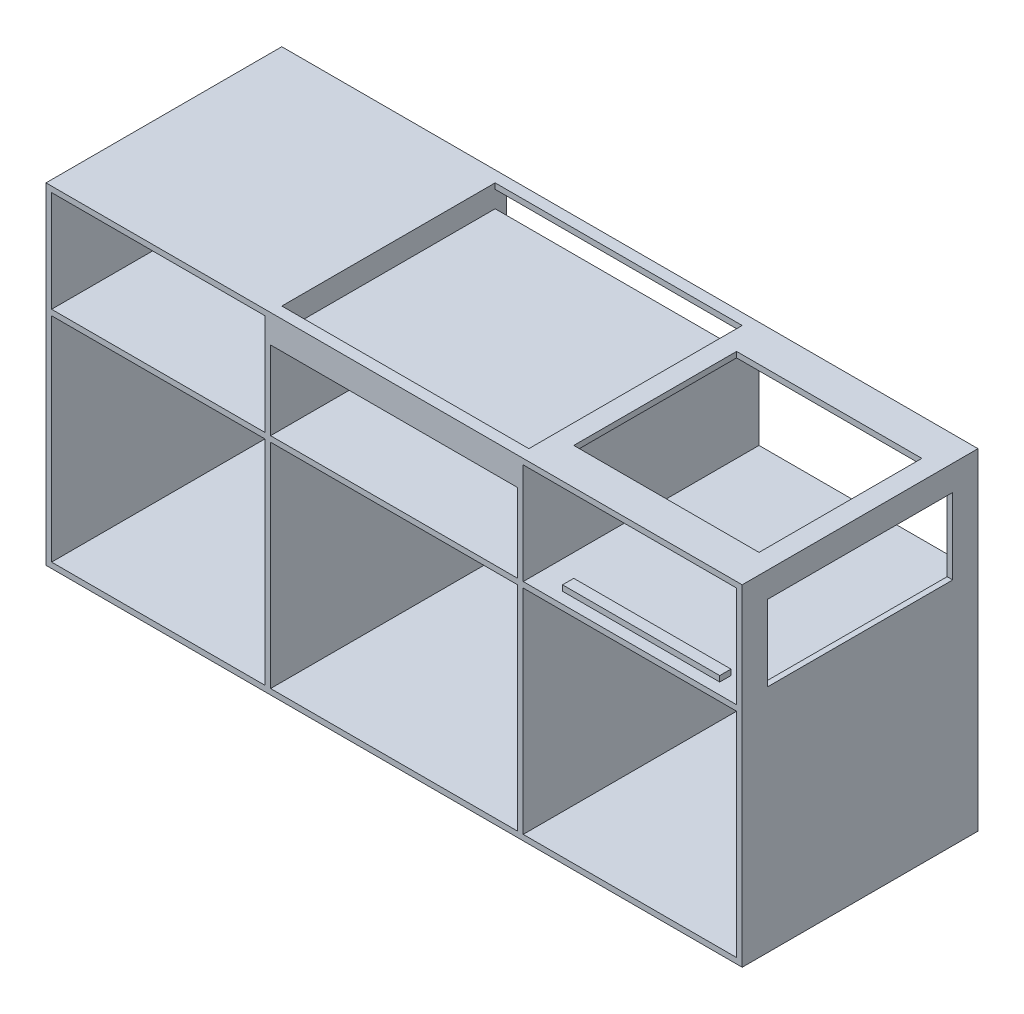
SolidWorks part; units mm, degrees
material "Erable"
ref_plane "Plan de face" through (0, 0, 0) normal (0, 0, 1) x (1, 0, 0)
ref_plane "Plan de dessus" through (0, 0, 0) normal (0, 1, 0) x (1, 0, 0)
ref_plane "Plan de droite" through (0, 0, 0) normal (1, 0, 0) x (0, 0, -1)
sketch "base" plane through (0, 0, 0) normal (0, 1, 0) x (1, 0, 0)
  line L0 (-3.1738, 188.5224) -> (-3.1738, -231.4776) construction
  line L1 (-613.1738, 188.5224) -> (606.8262, 188.5224)
  line L2 (-613.1738, 188.5224) -> (-613.1738, -231.4776)
  line L3 (-613.1738, -231.4776) -> (606.8262, -231.4776)
  line L4 (606.8262, 188.5224) -> (606.8262, -231.4776)
  line L5 (606.8262, -231.4776) -> (616.8262, -231.4776)
  line L6 (-613.1738, 188.5224) -> (-623.1738, 188.5224)
  line L7 (-613.1738, 188.5224) -> (-613.1738, -231.4776)
  line L8 (-613.1738, -231.4776) -> (-623.1738, -231.4776)
  line L9 (-623.1738, 188.5224) -> (-623.1738, -231.4776)
  line L10 (606.8262, 188.5224) -> (616.8262, 188.5224)
  line L11 (616.8262, 188.5224) -> (616.8262, -231.4776)
  line L13 (-233.1738, 188.5224) -> (-223.1738, 188.5224)
  line L14 (-233.1738, 188.5224) -> (-233.1738, -231.4776)
  line L15 (-233.1738, -231.4776) -> (-223.1738, -231.4776)
  line L16 (-223.1738, 188.5224) -> (-223.1738, -231.4776)
  line L17 (216.8262, 188.5224) -> (226.8262, 188.5224)
  line L18 (216.8262, 188.5224) -> (216.8262, -231.4776)
  line L19 (216.8262, -231.4776) -> (226.8262, -231.4776)
  line L20 (226.8262, 188.5224) -> (226.8262, -231.4776)
  dimension "D1" = 1220
  dimension "D2" = 420
  dimension "D3" = 10
  dimension "D4" = 10
  dimension "D5" = 380
  dimension "D6" = 10
  dimension "D7" = 380
extrude "planche_bas" add sketch "base" along normal blind 10 contours L1 L0 L3 L18 | L0 L1 L16 L3 | L1 L20 L3 L4 | L14 L1 L2 L3 region at (106.8262, 0, 21.4776) region at (-113.1738, 0, 21.4776) region at (-423.1738, 0, 21.4776) region at (416.8262, 0, 21.4776)
extrude "panneaux_lateraux" add sketch "base<6>" along normal blind 580 contours L11 L10 L4 L5 | L6 L9 L8 L2 region at (-618.1738, 0, 21.4776) region at (611.8262, 0, 21.4776)
sketch "base<6>" plane through (0, 0, 0) normal (0, 1, 0) x (1, 0, 0) same geometry as "base"
extrude "panneaux_bas_inter" add sketch "base<7>" along normal blind 390 contours L20 L1 L18 L3 | L16 L15 L14 L13 region at (221.8262, 0, 21.4776)
sketch "base<7>" plane through (0, 0, 0) normal (0, 1, 0) x (1, 0, 0) same geometry as "base"
ref_plane "Plan1" through (0, 390, 0) normal (0, 1, 0) x (1, 0, 0)
sketch "Esquisse2" plane through (0, 390, 0) normal (0, 1, 0) x (1, 0, 0)
  line L1 (-613.1738, 188.5224) -> (606.8262, 188.5224)
  line L2 (-613.1738, 188.5224) -> (-613.1738, -231.4776)
  line L3 (-613.1738, -231.4776) -> (606.8262, -231.4776)
  line L4 (606.8262, 188.5224) -> (606.8262, -231.4776)
  line L5 (-233.1738, 188.5224) -> (-223.1738, 188.5224)
  line L6 (-233.1738, 188.5224) -> (-233.1738, -231.4776)
  line L7 (-233.1738, -231.4776) -> (-223.1738, -231.4776)
  line L8 (-223.1738, 188.5224) -> (-223.1738, -231.4776)
  line L9 (216.8262, 188.5224) -> (226.8262, 188.5224)
  line L10 (216.8262, 188.5224) -> (216.8262, -231.4776)
  line L11 (216.8262, -231.4776) -> (226.8262, -231.4776)
  line L12 (226.8262, 188.5224) -> (226.8262, -231.4776)
  line L13 (276.8262, -191.4776) -> (556.8262, -191.4776)
  line L14 (276.8262, -191.4776) -> (276.8262, -211.4776)
  line L15 (276.8262, -211.4776) -> (556.8262, -211.4776)
  line L16 (556.8262, -191.4776) -> (556.8262, -211.4776)
  dimension "D1" = 50
  dimension "D2" = 50
  dimension "D3" = 20
  dimension "D4" = 20
extrude "Boss.-Extru.9" add sketch "Esquisse2" along normal blind 10 separate body contours L6 L1 L2 L3 | L10 L1 L8 L3 | L1 L12 L3 L4 region at (-423.1738, 390, 21.4776) region at (-3.1738, 390, 21.4776) region at (416.8262, 390, 14.9322)
extrude "Boss.-Extru.10" add sketch "Esquisse2<4>" along normal blind 190 contours L8 L7 L6 L5 | L10 L11 L12 L9
sketch "Esquisse2<4>" plane through (0, 390, 0) normal (0, 1, 0) x (1, 0, 0) same geometry as "Esquisse2"
ref_plane "Plan7" through (0, 580, 0) normal (0, 1, 0) x (1, 0, 0)
sketch "Esquisse5" plane through (0, 580, 0) normal (0, 1, 0) x (1, 0, 0)
  line L1 (-623.1738, 188.5224) -> (616.8262, 188.5224)
  line L2 (-623.1738, 188.5224) -> (-623.1738, -231.4776)
  line L3 (-623.1738, -231.4776) -> (616.8262, -231.4776)
  line L4 (616.8262, 188.5224) -> (616.8262, -231.4776)
  line L5 (251.8262, 123.5224) -> (581.8262, 123.5224)
  line L6 (251.8262, 123.5224) -> (251.8262, -166.4776)
  line L7 (251.8262, -166.4776) -> (581.8262, -166.4776)
  line L8 (581.8262, 123.5224) -> (581.8262, -166.4776)
  line L9 (-223.1738, 168.5224) -> (216.8262, 168.5224)
  line L10 (-223.1738, 168.5224) -> (-223.1738, -211.4776)
  line L11 (-223.1738, -211.4776) -> (216.8262, -211.4776)
  line L12 (216.8262, 168.5224) -> (216.8262, -211.4776)
  dimension "D1" = 35
  dimension "D2" = 65
  dimension "D3" = 65
  dimension "D4" = 330
  dimension "D5" = 20
  dimension "D6" = 20
  dimension "D7" = 35
  dimension "D8" = 440
extrude "Boss.-Extru.11" add sketch "Esquisse5" along normal blind 10
ref_plane "Plan8" through (0, 550, 0) normal (0, 1, 0) x (1, 0, 0)
sketch "Esquisse7" plane through (0, 550, 0) normal (0, 1, 0) x (1, 0, 0)
  line L1 (-223.1738, 168.5224) -> (216.8262, 168.5224)
  line L2 (-223.1738, 168.5224) -> (-223.1738, -211.4776)
  line L3 (-223.1738, -211.4776) -> (216.8262, -211.4776)
  line L4 (216.8262, 168.5224) -> (216.8262, -211.4776)
  line L5 (-223.1738, -211.4776) -> (216.8262, -211.4776)
  line L6 (-223.1738, -211.4776) -> (-223.1738, -231.4776)
  line L7 (-223.1738, -231.4776) -> (216.8262, -231.4776)
  line L8 (216.8262, -211.4776) -> (216.8262, -231.4776)
extrude "Boss.-Extru.12" add sketch "Esquisse7" against normal blind 10 contours L4 L1 L2 L3 region at (-3.1738, 550, 21.4776)
extrude "Boss.-Extru.13" add sketch "Esquisse7<3>" along normal blind 30 and the other way blind 10 contours L8 L3 L6 L7 region at (-3.1738, 550, 221.4776)
sketch "Esquisse7<3>" plane through (0, 550, 0) normal (0, 1, 0) x (1, 0, 0) same geometry as "Esquisse7"
sketch "Esquisse8" plane through (616.8262, 0, 0) normal (1, 0, 0) x (0, 0, -1)
  line L0 (-231.4776, 590) -> (188.5224, 590) construction
  line L1 (-186.4776, 545) -> (143.5224, 545)
  line L2 (-186.4776, 545) -> (-186.4776, 410)
  line L3 (-186.4776, 410) -> (143.5224, 410)
  line L4 (143.5224, 545) -> (143.5224, 410)
  line L5 (-231.4776, 590) -> (-231.4776, 0) construction
  line L6 (188.5224, 590) -> (188.5224, 0) construction
  dimension "D1" = 45
  dimension "D2" = 330
  dimension "D3" = 45
  dimension "D4" = 45
  dimension "D5" = 135
extrude "Enlèv. mat.-Extru.3" cut sketch "Esquisse8" against normal blind 10
extrude "Boss.-Extru.14" add sketch "Esquisse2<5>" along normal blind 20 contours L15 L16 L13 L14
sketch "Esquisse2<5>" plane through (0, 390, 0) normal (0, 1, 0) x (1, 0, 0) same geometry as "Esquisse2"
